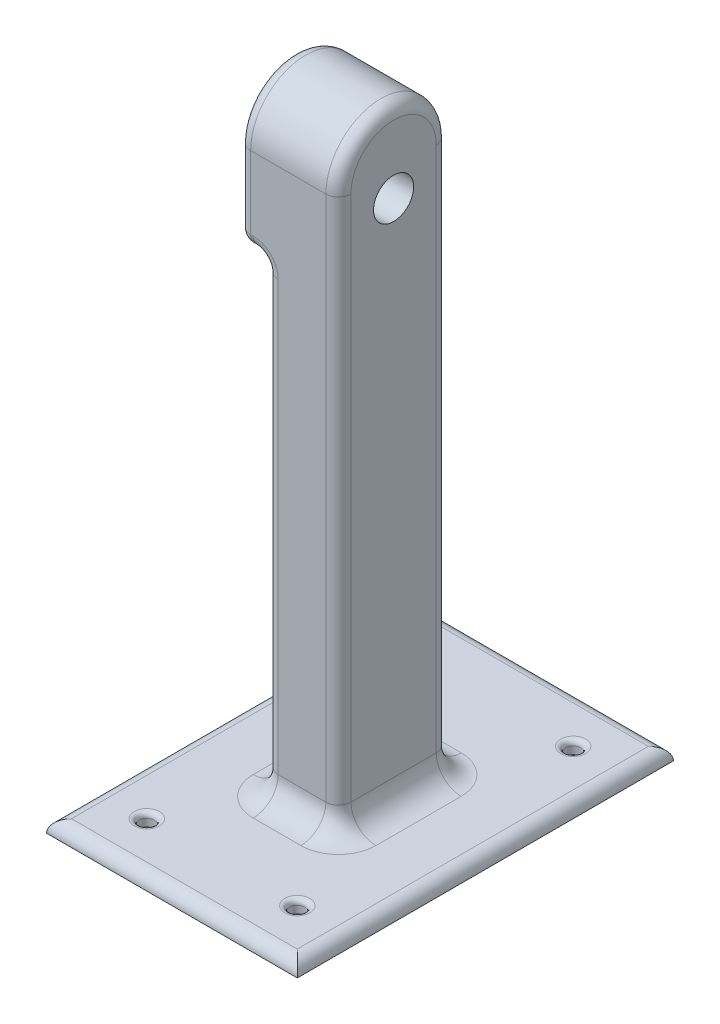
SolidWorks part; units mm, degrees
ref_plane "Front Plane" through (0, 0, 0) normal (0, 0, 1) x (1, 0, 0)
ref_plane "Top Plane" through (0, 0, 0) normal (0, 1, 0) x (1, 0, 0)
ref_plane "Right Plane" through (0, 0, 0) normal (1, 0, 0) x (0, 0, -1)
sketch "Sketch1" plane through (0, 0, 0) normal (0, 1, 0) x (1, 0, 0)
  line L0 (50, 0) -> (50, -158.6751) construction
  line L1 (0, 0) -> (100, 0)
  line L2 (0, 0) -> (0, -150)
  line L3 (0, -150) -> (100, -150)
  line L4 (100, 0) -> (100, -150)
  line L5 (0, -75) -> (100, -75) construction
  circle A0 centre (20, -20) radius 3
  circle A1 centre (80, -20) radius 3
  circle A2 centre (80, -130) radius 3
  circle A3 centre (20, -130) radius 3
  dimension "D3" = 6
  dimension "D1" = 150
  dimension "D2" = 100
  dimension "D4" = 20
  dimension "D5" = 20
extrude "bottom" add sketch "Sketch1" along normal blind 5
sketch "Sketch2" plane through (0, 5, 0) normal (0, 1, 0) x (1, 0, 0)
  line L0 (35.9591, -54.5588) -> (35.9591, -98.5588)
  line L1 (39.9591, -58.5588) -> (60.9591, -58.5588)
  line L2 (39.9591, -58.5588) -> (39.9591, -94.5588)
  line L3 (39.9591, -94.5588) -> (60.9591, -94.5588)
  line L4 (60.9591, -58.5588) -> (60.9591, -94.5588)
  line L5 (35.9591, -98.5588) -> (64.9591, -98.5588)
  line L6 (64.9591, -54.5588) -> (64.9591, -98.5588)
  line L7 (35.9591, -54.5588) -> (64.9591, -54.5588)
  dimension "D1" = 36
  dimension "D2" = 21
  dimension "D3" = 4
extrude "Boss-Extrude2" add sketch "Sketch2" along normal blind 190 contours L4 L1 L2 L3 | L0 L5 L6 L7 region at (50.4591, 5, 76.5588)
sketch "Sketch3" plane through (64.9591, 0, 0) normal (1, 0, 0) x (0, 0, -1)
  line L0 (-98.5588, 195) -> (-98.5588, 225)
  line L1 (-54.5588, 225) -> (-54.5588, 195)
  line L2 (-54.5588, 195) -> (-98.5588, 195)
  arc A0 (-98.5588, 225) -> (-54.5588, 225) centre (-76.5588, 225) cw
  dimension "D1" = 30
extrude "Boss-Extrude3" add sketch "Sketch3" against normal blind 40
sketch "Sketch4" plane through (64.9591, 0, 0) normal (1, 0, 0) x (0, 0, -1)
  line L3 (-98.5588, 225) -> (-98.5588, 5) construction
  line L4 (-150, 5) -> (0, 5) construction
  circle A1 centre (-76.5588, 215) radius 8
  dimension "D2" = 16
  dimension "D1" = 22
  dimension "D3" = 210
extrude "Cut-Extrude1" cut sketch "Sketch4" against normal up to surface (40 mm away) up to face at (24.9591, 215.5, 76.5588)
sketch "Sketch5" plane through (0, 195, 0) normal (0, -1, 0) x (1, 0, 0)
  line L1 (24.9591, 98.5588) -> (64.9591, 98.5588)
  line L2 (24.9591, 98.5588) -> (24.9591, 54.5588)
  line L3 (24.9591, 54.5588) -> (64.9591, 54.5588)
  line L4 (64.9591, 98.5588) -> (64.9591, 54.5588)
  dimension "D1" = 40
  dimension "D2" = 44
extrude "Boss-Extrude4" add sketch "Sketch5" along normal blind 4
fillet "Fillet1" radius 5 10 edges at (24.9591, 247, 76.5588) (24.9591, 208, 98.5588) (24.9591, 191, 76.5588) (24.9591, 208, 54.5588) (24.9591, 215, 84.5588) (35.9591, 98, 98.5588) (35.9591, 98, 54.5588) (30.4591, 191, 98.5588) (30.4591, 191, 54.5588) (35.9591, 191, 76.5588)
fillet "Fillet2" radius 5 3 edges at (64.9591, 115, 54.5588) (64.9591, 247, 76.5588) (64.9591, 115, 98.5588)
fillet "Fillet3" radius 10 8 edges at (37.4236, 5, 97.0943) (35.9591, 5, 76.5588) (37.4236, 5, 56.0233) (50.4591, 5, 54.5588) (63.4946, 5, 56.0233) (64.9591, 5, 76.5588) (63.4946, 5, 97.0943) (50.4591, 5, 98.5588)
fillet "Fillet4" radius 5 4 edges at (50, 5, 150) (100, 5, 75) (50, 5, 0) (0, 5, 75)
fillet "Fillet5" radius 2 4 edges at (80, 5, 17) (20, 5, 23) (20, 5, 127) (80, 5, 133)
